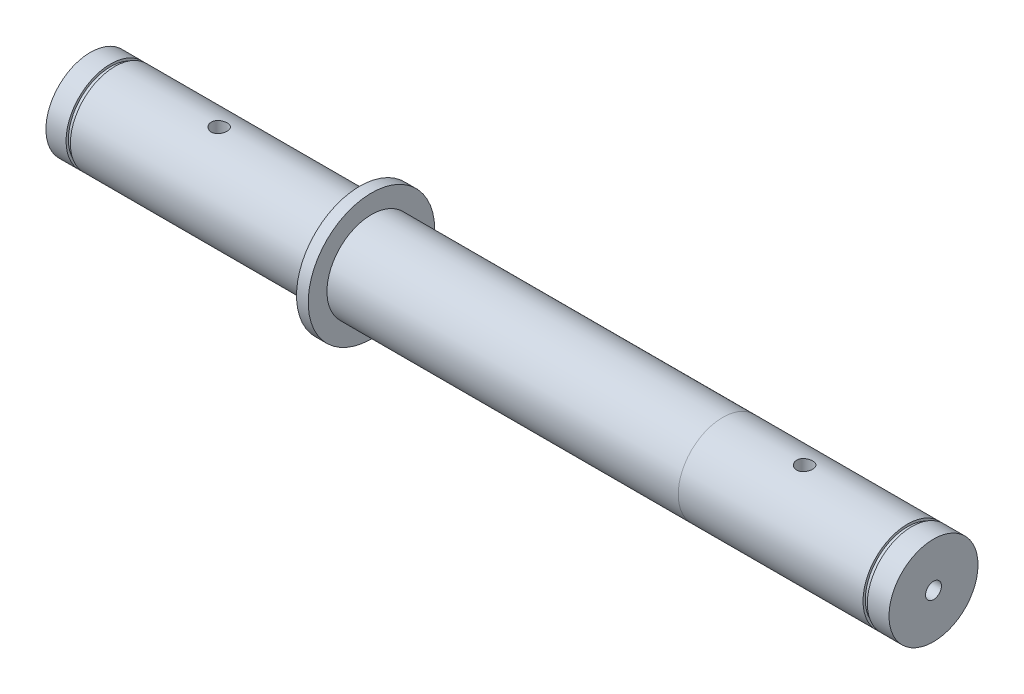
SolidWorks part; units mm, degrees
material "1.7225 (42CrMo4)"
ref_plane "E_Oben" through (0, 0, 0) normal (0, 0, 1) x (1, 0, 0)
ref_plane "E_Vorne" through (0, 0, 0) normal (0, 1, 0) x (1, 0, 0)
ref_plane "E_Rechts" through (0, 0, 0) normal (1, 0, 0) x (0, 0, -1)
ref_axis "A_Drehachse" through (-88.99, 0, 0) along (1, 0, 0)
sketch "Skizze1" plane through (0, 0, 0) normal (0, 0, 1) x (1, 0, 0)
  line L1 (0, -55) -> (0, 55) construction
  line L3 (180, 19) -> (180, 0)
  line L4 (180, 0) -> (-180, 0)
  line L7 (-180, 19) -> (-180, 0)
  line L10 (-65, 19) -> (-65, 27)
  line L11 (-65, 27) -> (-60, 27)
  line L12 (-60, 27) -> (-60, 19.0001)
  line L13 (-180, 19) -> (-65, 19)
  line L14 (-60, 19.0001) -> (90, 19.0001)
  line L15 (90, 19.0001) -> (90, 19)
  line L16 (90, 19) -> (180, 19)
  point P12 (0, 0)
  point P19 (-62.5, 27)
  dimension "D1" = 19.0001
  dimension "D2" = 19
  dimension "D3" = 19
  dimension "D4" = 360
  dimension "D5" = 115
  dimension "D6" = 5
  dimension "D7" = 27
  dimension "D8" = 150
revolve "Rotation1" add sketch "Skizze1" angle 360 about L4
hole_wizard "M8 Gewindebohrung1" positions "Skizze13" profile "Skizze14" tap size "M8" standard "DIN"
sketch "Skizze13" plane through (180, 0, 0) normal (1, 0, 0) x (0, 0, -1)
  point P0 (0, 0)
  point P3 (0, 0)
sketch "Skizze14" plane through (180, 0, 0) normal (0, 1, 0) x (0, 0, -1)
  line L0 (0, 0) -> (0, 327.0429)
  line L1 (0, 327.0429) -> (3.4, 325)
  line L2 (3.4, 325) -> (3.4, 0)
  line L5 (3.4, 0) -> (0, 0)
  line L10 (0, 327.0429) -> (-3.4, 325) construction
  line L11 (0, -6.35) -> (0, 107.95) construction
  dimension "Bohrerdurchmesser" = 6.8
  dimension "Bohrungstiefe" = 325
  dimension "Spitzenwinkel" = 118
cosmetic thread "Bohrungsgewinde2" parameters "D1"=20, "D2"=8
hole_wizard "M8 Gewindebohrung3" positions "Skizze17" profile "Skizze18" tap size "M8" standard "DIN" end condition through all
sketch "Skizze17" plane through (0, 0, 0) normal (0, 1, 0) x (1, 0, 0)
  line L0 (-55, 0) -> (55, 0) construction
  line L1 (-88.99, 0) -> (88.99, 0) construction
  line L3 (180, -19) -> (180, 19) construction
  point P0 (-125, 0)
  point P4 (125, 0)
  dimension "D3" = 305
  dimension "D4" = 55
sketch "Skizze18" plane through (-125, 0, 0) normal (1, 0, 0) x (0, 0, -1)
  line L0 (0, 0) -> (0, 27)
  line L1 (0, 27) -> (3.4, 27)
  line L2 (3.4, 27) -> (3.4, 0)
  line L5 (3.4, 0) -> (0, 0)
  line L11 (0, -6.35) -> (0, 107.95) construction
  dimension "Bohrerdurchmesser" = 6.8
  dimension "Bohrungstiefe" = 27
mirror "Spiegeln2" about plane through (0, 0, 0) normal (0, 1, 0) of "M8 Gewindebohrung3"
sketch "Skizze19" plane through (0, 0, 0) normal (0, 0, 1) x (1, 0, 0)
  line L8 (180, 19) -> (128.4, 19) construction
  line L9 (168.9, 19) -> (170.75, 19)
  line L10 (168.9, 19) -> (168.9, 18)
  line L11 (168.9, 18) -> (170.75, 18)
  line L12 (170.75, 19) -> (170.75, 18)
  line L13 (180, -19) -> (180, 19) construction
  dimension "D1" = 9.25
  dimension "D2" = 1
  dimension "D4" = 1.85
revolve "Schnitt-Rotation1" cut sketch "Skizze19" angle 360 about axis through (-88.99, 0, 0) along (1, 0, 0)
sketch "Skizze20" plane through (0, 0, 0) normal (0, 0, 1) x (1, 0, 0)
  line L9 (-128.3999, 19) -> (-180, 19) construction
  line L10 (-180, 19) -> (-180, -19) construction
  line L11 (-171.4, 19) -> (-169.55, 19)
  line L12 (-171.4, 19) -> (-171.4, 18)
  line L13 (-171.4, 18) -> (-169.55, 18)
  line L14 (-169.55, 19) -> (-169.55, 18)
  dimension "D1" = 8.6
  dimension "D4" = 1
  dimension "D5" = 1.85
revolve "Schnitt-Rotation2" cut sketch "Skizze20" angle 360 about axis through (-88.99, 0, 0) along (1, 0, 0)
